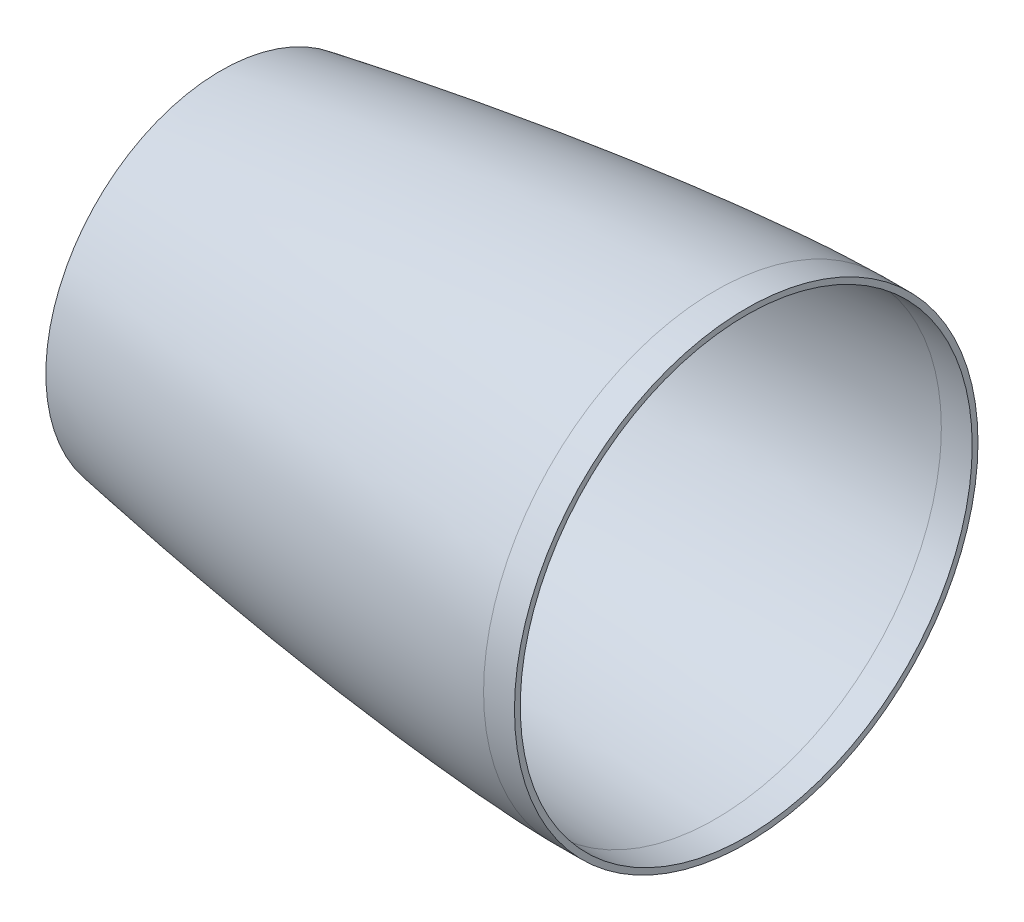
SolidWorks part; units mm, degrees
ref_plane "Front Plane" through (0, 0, 0) normal (0, 0, 1) x (1, 0, 0)
ref_plane "Top Plane" through (0, 0, 0) normal (0, 1, 0) x (1, 0, 0)
ref_plane "Right Plane" through (0, 0, 0) normal (1, 0, 0) x (0, 0, -1)
sketch "Sketch1" plane through (0, 0, 0) normal (0, 0, 1) x (1, 0, 0)
  line L0 (0, 0) -> (457.2, 0) construction
  line L2 (457.2, 95.25) -> (457.2, 0) construction
  line L3 (457.2, 0) -> (0, 0)
  line L5 (457.2, 0) -> (469.9, 0)
  line L7 (457.2, 95.25) -> (469.9, 95.25)
  line L8 (469.9, 0) -> (469.9, 95.25)
  spline S0 degree 4 poles (0, 0) (0.0023, 0.0126) (0.0082, 0.0373) (0.0262, 0.085) (0.0706, 0.1767) (0.1354, 0.2842) (0.2204, 0.4066) (0.336, 0.5565) (0.5083, 0.7608) (0.8021, 1.0733) (1.3251, 1.5652) (2.2381, 2.3192) (3.8253, 3.4666) (6.614, 5.2253) (11.4561, 7.8766) (19.2936, 11.6017) (32.6156, 17.1305) (51.6883, 23.9819) (75.6131, 31.5462) (103.3102, 39.362) (131.8924, 46.6864) (160.6143, 53.4403) (189.4482, 59.6969) (218.3767, 65.4994) (247.3876, 70.874) (276.4727, 75.8318) (305.6259, 80.3722) (334.843, 84.4812) (364.1216, 88.1294) (389.7928, 90.8706) (411.8341, 92.8374) (428.9951, 94.0676) (440.0323, 94.6976) (448.6181, 95.062) (453.5214, 95.2002) (455.9737, 95.2443) (457.2, 95.25) knots 0 0 0 0 0 0.000108 0.000216 0.000433 0.000866 0.001175 0.001483 0.002044 0.003139 0.004822 0.007588 0.012112 0.019791 0.032854 0.05453 0.085907 0.142462 0.205216 0.267971 0.330725 0.393479 0.456233 0.518987 0.581741 0.644496 0.70725 0.770004 0.832758 0.895512 0.926889 0.958267 0.979133 0.989567 1 1 1 1 1 construction
  spline S1 degree 4 poles (0, 0) (0.0023, 0.0126) (0.0082, 0.0373) (0.0262, 0.085) (0.0706, 0.1767) (0.1354, 0.2842) (0.2204, 0.4066) (0.336, 0.5565) (0.5083, 0.7608) (0.8021, 1.0733) (1.3251, 1.5652) (2.2381, 2.3192) (3.8253, 3.4666) (6.614, 5.2253) (11.4561, 7.8766) (19.2936, 11.6017) (32.6156, 17.1305) (51.6883, 23.9819) (75.6131, 31.5462) (103.3102, 39.362) (131.8924, 46.6864) (160.6143, 53.4403) (189.4482, 59.6969) (218.3767, 65.4994) (247.3876, 70.874) (276.4727, 75.8318) (305.6259, 80.3722) (334.843, 84.4812) (364.1216, 88.1294) (389.7928, 90.8706) (411.8341, 92.8374) (428.9951, 94.0676) (440.0323, 94.6976) (448.6181, 95.062) (453.5214, 95.2002) (455.9737, 95.2443) (457.2, 95.25) knots 0 0 0 0 0 0.000108 0.000216 0.000433 0.000866 0.001175 0.001483 0.002044 0.003139 0.004822 0.007588 0.012112 0.019791 0.032854 0.05453 0.085907 0.142462 0.205216 0.267971 0.330725 0.393479 0.456233 0.518987 0.581741 0.644496 0.70725 0.770004 0.832758 0.895512 0.926889 0.958267 0.979133 0.989567 1 1 1 1 1
  dimension "D1" = 457.2
  dimension "D2" = 95.25
  dimension "D3" = 12.7
revolve "Revolve1" add sketch "Sketch1" angle 360 about L3
shell "Shell1" thickness 2.3813 removed face at (469.9, 0, -95.25)
ref_plane "Plane1" through (0, 0, 0) normal (1, 0, 0) x (0, 0, -1)
sketch "Sketch3" plane through (0, 0, 0) normal (1, 0, 0) x (0, 0, -1)
  circle A0 centre (0, 0) radius 95.25
extrude "Cut-Extrude1" cut sketch "Sketch3" along normal blind 254
